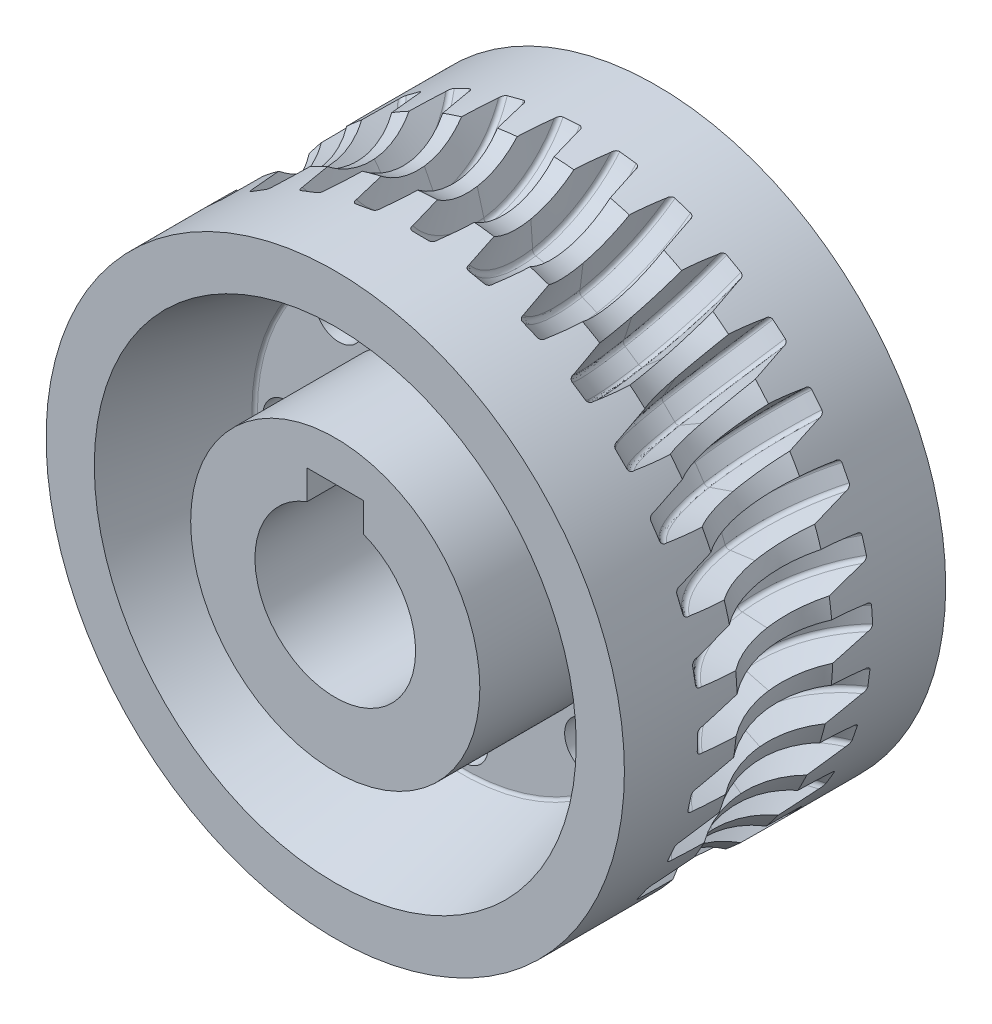
SolidWorks part; units mm, degrees
note: The reader was unsure of these and kept them because the rebuilt part matched: shared geometry of "Sketch9<2>".
ref_plane "Front Plane" through (0, 0, 0) normal (0, 0, 1) x (1, 0, 0)
ref_plane "Top Plane" through (0, 0, 0) normal (0, 1, 0) x (1, 0, 0)
ref_plane "Right Plane" through (0, 0, 0) normal (1, 0, 0) x (0, 0, -1)
sketch "Sketch3" plane through (0, 0, 0) normal (1, 0, 0) x (0, 0, -1)
  line L0 (-11.0435, 0) -> (10.8311, 0) construction
  line L1 (0, 0) -> (0, 5) construction
  line L2 (-10, 5) -> (10, 5)
  line L3 (-10, 5) -> (-10, 9)
  line L4 (10, 5) -> (10, 9)
  line L5 (-10, 9) -> (-2, 9)
  line L6 (10, 9) -> (2, 9)
  line L7 (-2, 9) -> (-2, 13)
  line L8 (2, 9) -> (2, 13)
  line L9 (-2, 13) -> (-10, 15)
  line L10 (2, 13) -> (10, 15)
  line L11 (-10, 15) -> (-10, 20)
  line L12 (10, 15) -> (10, 20)
  line L13 (-10, 20) -> (10, 20)
  point P24 (0, 5)
  dimension "D1" = 20
  dimension "D2" = 18
  dimension "D3" = 4
  dimension "D4" = 30
  dimension "D5" = 40
  dimension "D6" = 10
  dimension "D7" = 8
revolve "Revolve1" add sketch "Sketch3" angle 360 about L0
sketch "Sketch4" plane through (0, 0, 0) normal (1, 0, 0) x (0, 0, -1)
  line L0 (-24.9801, 0) -> (24.9801, 0) construction
  line L1 (2.9762, 18) -> (10, 18)
  line L7 (-10, 20) -> (-10, 18)
  line L8 (-10, 20) -> (-10, -20) construction
  line L9 (-10, 18) -> (-2.9762, 18)
  line L10 (10, -20) -> (10, 20) construction
  line L11 (10, 18) -> (10, 20)
  line L12 (10, 20) -> (-2.5524, 20)
  line L13 (-2.5524, 20) -> (-10, 20)
  arc A2 (-2.9762, 18) -> (2.9762, 18) centre (0, 22.0178) ccw
  point P6 (0, 0)
  dimension "D1" = 2
revolve "Cut-Revolve4" cut sketch "Sketch4" angle 360 about L0
sketch "Sketch5" plane through (0, 0, -10) normal (0, 0, -1) x (-1, 0, 0)
  line L0 (0, 0) -> (0, 6.5) construction
  line L5 (-1.75, 6.5) -> (1.75, 6.5)
  line L6 (-1.75, 6.5) -> (-1.75, 0)
  line L7 (-1.75, 0) -> (1.75, 0)
  line L8 (1.75, 6.5) -> (1.75, 0)
  circle A0 centre (0, 0) radius 5 construction
  point P4 (0, 0)
  point P8 (0, 5)
  dimension "D1" = 3.5
  dimension "D2" = 1.5
extrude "Cut-Extrude1" cut sketch "Sketch5" against normal up to next
sketch "Sketch8" plane through (0, 0, 0) normal (1, 0, 0) x (0, 0, -1)
  circle A0 centre (0, -22.0178) radius 5
  arc A1 (2.9762, -18) -> (-2.9762, -18) centre (0, -22.0178) ccw construction
  dimension "D1" = 10
curve "Helix/Spiral1" pitch 5 height 1.25 turns 0.25
sketch "Sketch9" plane through (0, 0, 0) normal (0, 0, 1) x (1, 0, 0)
  line L0 (0, -17.0178) -> (0, -15.2417) construction
  line L1 (-0.5, -15.2417) -> (0.5, -15.2417)
  line L2 (-0.75, -15.4917) -> (-1.1521, -17.0178)
  line L3 (-1.1521, -17.0178) -> (-1.1521, -18.4629)
  line L4 (1.1719, -17.0178) -> (0.75, -15.4917)
  line L5 (-1.1521, -18.4629) -> (1.1719, -18.4629)
  line L6 (1.1719, -18.4629) -> (1.1719, -17.0178)
  arc A0 (0.75, -15.4917) -> (0.5, -15.2417) centre (0.5, -15.4917) ccw
  arc A1 (-0.5, -15.2417) -> (-0.75, -15.4917) centre (-0.5, -15.4917) ccw
  spline S0 degree 3 poles (0, -17.0178) (0.1035, -17.0178) (0.3128, -17.278) (0.625, -18.3907) (0.9372, -20.0527) (1.1465, -21.3674) (1.25, -22.0178) knots 0 0 0 0 0.25 0.5 0.75 1 1 1 1 construction
  point P8 (0, -15.2417)
  dimension "D1" = 0.5
  dimension "D2" = 1
sweep "Cut-Sweep1" cut profiles "Sketch9" path "Helix/Spiral1"
sketch "Sketch10" plane through (0, 0, 0) normal (1, 0, 0) x (0, 0, -1)
  circle A2 centre (0, -22.0178) radius 5
  arc A3 (0, -17.0178) -> (-2.9762, -18) centre (0, -22.0178) ccw construction
  dimension "D1" = 10
curve "Helix/Spiral2" pitch 5 height 1.25 turns 0.25
sweep "Cut-Sweep2" cut profiles "Sketch9<2>" path "Helix/Spiral2"
sketch "Sketch9<2>" plane through (0, 0, 0) normal (0, 0, 1) x (1, 0, 0) same geometry as "Sketch9"
pattern_circular "CirPattern1" count 32 over 360 about axis through (0, 0, 11.0435) along (0, 0, 1) of "Cut-Sweep1", "Cut-Sweep2"
sketch "Sketch11" plane through (0, 0, -2) normal (0, 0, -1) x (-1, 0, 0)
  line L0 (0, 9) -> (0, 13) construction
  circle A0 centre (0, 0) radius 9 construction
  circle A1 centre (0, 0) radius 9 construction
  circle A2 centre (0, 0) radius 13 construction
  circle A3 centre (0, 11) radius 1.5
  dimension "D1" = 3
extrude "Cut-Extrude2" cut sketch "Sketch11" against normal up to next contours A3
pattern_circular "CirPattern2" count 8 over 360 about axis through (0, 0, 0) along (0, 0, 1) of "Cut-Extrude2"
fillet "Fillet1" radius 0.2 2 edges at (13, 0, -2) (13, 0, 2)
